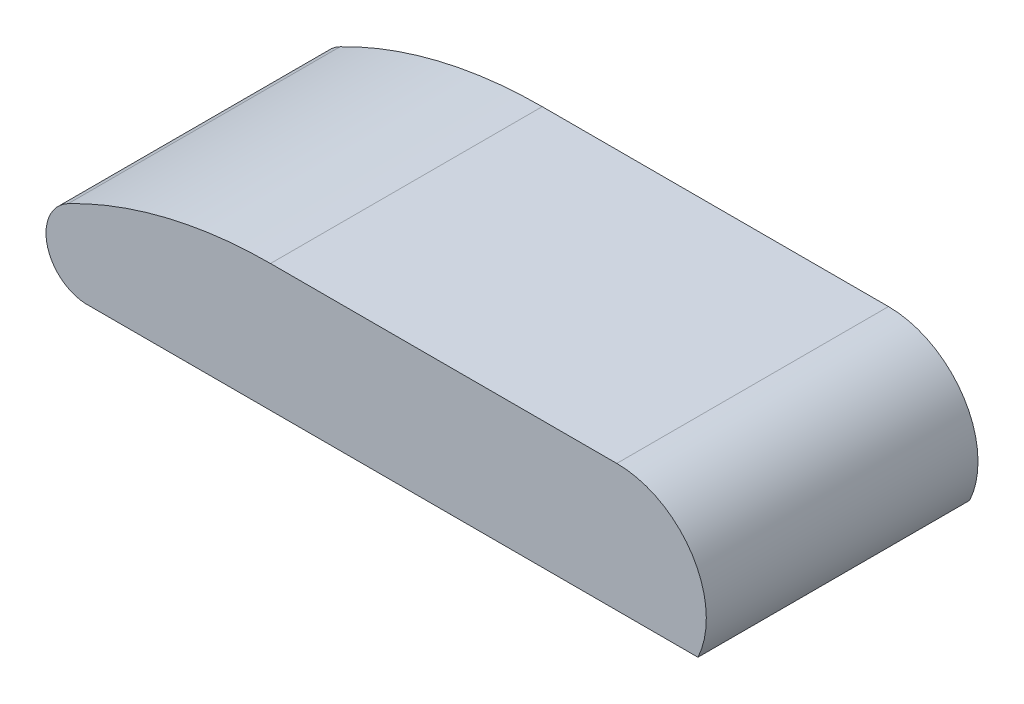
SolidWorks part; units mm, degrees
ref_plane "Front Plane" through (0, 0, 0) normal (0, 0, 1) x (1, 0, 0)
ref_plane "Top Plane" through (0, 0, 0) normal (0, 1, 0) x (1, 0, 0)
ref_plane "Right Plane" through (0, 0, 0) normal (1, 0, 0) x (0, 0, -1)
sketch "Sketch1" plane through (0, 0, 0) normal (0, 0, 1) x (1, 0, 0)
  line L1 (77.813, -3.2432) -> (72.7051, -3.2428)
  line L4 (77.813, -3.2432) -> (77.8131, -1.7432) construction
  line L5 (-11.687, -3.2364) -> (-11.6869, -1.7364) construction
  line L7 (66.52, 13.5) -> (15.54, 13.5)
  line L8 (78.4684, -4.2432) -> (72.705, -4.2428)
  line L9 (66.52, 14.5) -> (15.54, 14.5)
  line L10 (77.813, -3.2432) -> (72.7051, -3.2428)
  line L11 (72.7051, -3.2428) -> (72.705, -4.2428)
  line L12 (-11.687, -3.2364) -> (-6.5903, -3.2368)
  line L13 (-6.5903, -3.2368) -> (-6.5904, -4.2368)
  line L15 (-6.5904, -4.2368) -> (-11.7115, -4.2364)
  line L16 (-6.5903, -3.2368) -> (-11.687, -3.2364)
  line L17 (78.4684, -4.2432) -> (-11.7115, -4.2364) construction
  line L19 (77.813, -3.2432) -> (-11.687, -3.2364) construction
  arc A0 (66.52, 13.5) -> (77.813, -3.2432) centre (66.52, 1.32) cw
  arc A1 (15.54, 13.5) -> (-13.7656, 6.3686) centre (15.54, -50.2796) ccw
  arc A2 (-13.7656, 6.3686) -> (-11.687, -3.2364) centre (-11.4266, 1.8474) ccw
  arc A3 (66.52, 14.5) -> (78.4684, -4.2432) centre (66.52, 1.32) cw
  arc A4 (-14.225, 7.2568) -> (-11.7115, -4.2364) centre (-11.4266, 1.8474) ccw
  arc A5 (15.54, 14.5) -> (-14.225, 7.2568) centre (15.54, -50.2796) ccw
  point P3 (0, 0)
  point P4 (0, 0)
  dimension "D1" = 1
extrude "Boss-Extrude1" add sketch "Sketch1" along normal blind 38 contours L9 A5 A4 L15 L13 L12 A2 A1 L7 A0 L1 L11 L8 A3 region at (77.4387, 8.6844, 0)
sketch "Sketch2" plane through (0, 0, 0) normal (0, 0, -1) x (-1, 0, 0)
  line L0 (-72.705, -4.2428) -> (6.5904, -4.2368)
  line L8 (-15.54, 14.5) -> (-66.52, 14.5)
  line L9 (-78.4684, -4.2432) -> (-72.705, -4.2428)
  line L10 (-72.705, -4.2428) -> (-72.7051, -3.2428)
  line L11 (-72.7051, -3.2428) -> (-77.813, -3.2432)
  line L12 (-66.52, 13.5) -> (-15.54, 13.5)
  line L13 (11.687, -3.2364) -> (6.5903, -3.2368)
  line L14 (6.5903, -3.2368) -> (6.5904, -4.2368)
  line L15 (6.5904, -4.2368) -> (11.7115, -4.2364)
  line L16 (-15.54, 14.5) -> (-66.52, 14.5)
  line L17 (-78.4684, -4.2432) -> (-72.705, -4.2428)
  line L23 (6.5904, -4.2368) -> (11.7115, -4.2364)
  arc A6 (-66.52, 14.5) -> (-78.4684, -4.2432) centre (-66.52, 1.32) ccw
  arc A7 (-66.52, 13.5) -> (-77.813, -3.2432) centre (-66.52, 1.32) ccw
  arc A8 (13.7656, 6.3686) -> (-15.54, 13.5) centre (-15.54, -50.2796) ccw
  arc A9 (11.687, -3.2364) -> (13.7656, 6.3686) centre (11.4266, 1.8474) ccw
  arc A10 (11.7115, -4.2364) -> (14.225, 7.2568) centre (11.4266, 1.8474) ccw
  arc A11 (14.225, 7.2568) -> (-15.54, 14.5) centre (-15.54, -50.2796) ccw
  arc A12 (-66.52, 14.5) -> (-78.4684, -4.2432) centre (-66.52, 1.32) ccw
  arc A16 (11.7115, -4.2364) -> (14.225, 7.2568) centre (11.4266, 1.8474) ccw
  arc A17 (14.225, 7.2568) -> (-15.54, 14.5) centre (-15.54, -50.2796) ccw
  dimension "D1" = 0
extrude "Boss-Extrude2" add sketch "Sketch2" along normal blind 1
ref_plane "Plane1" through (0, 0, 19) normal (0, 0, 1) x (1, 0, 0)
mirror "Mirror1" about plane through (0, 0, 19) normal (0, 0, 1) of "Boss-Extrude2"
sketch "Sketch3" plane through (-0.0003, -4.2373, 0) normal (-0.0001, -1, 0) x (1, -0.0001, 0)
  line L0 (72.7053, 38) -> (72.7053, 0) construction
  line L1 (64.7053, 35) -> (-4.7112, 35)
  line L2 (64.7053, 35) -> (64.7053, 3)
  line L3 (64.7053, 3) -> (-4.7112, 3)
  line L4 (78.4687, 39) -> (-11.7112, 39)
  line L5 (-11.7112, 39) -> (-11.7112, -1)
  line L6 (-11.7112, -1) -> (78.4687, -1)
  line L7 (78.4687, -1) -> (78.4687, 39)
  line L8 (78.4687, 39) -> (-11.7112, 39)
  line L9 (-11.7112, 39) -> (-11.7112, -1)
  line L10 (-11.7112, -1) -> (78.4687, -1)
  line L11 (78.4687, -1) -> (78.4687, 39)
  line L12 (-4.7112, 35) -> (-4.7112, 3)
  line L13 (-14.2256, -1) -> (15.5389, -1) construction
  line L14 (15.5389, 39) -> (-14.2256, 39) construction
  dimension "D2" = 7
  dimension "D3" = 8
  dimension "D4" = 4
  dimension "D5" = 4
  dimension "D1" = 0
extrude "Boss-Extrude3" add sketch "Sketch3" along normal blind 1
chamfer "Chamfer1" distance 1 angle 45 8 edges at (-11.7116, -5.2364, 19) (-4.7116, -5.2369, 19) (29.9967, -5.2396, 3) (29.9967, -5.2396, 35) (64.7049, -5.2422, 19) (78.4683, -5.2432, 19) (33.3784, -5.2398, 39) (33.3784, -5.2398, -1)
